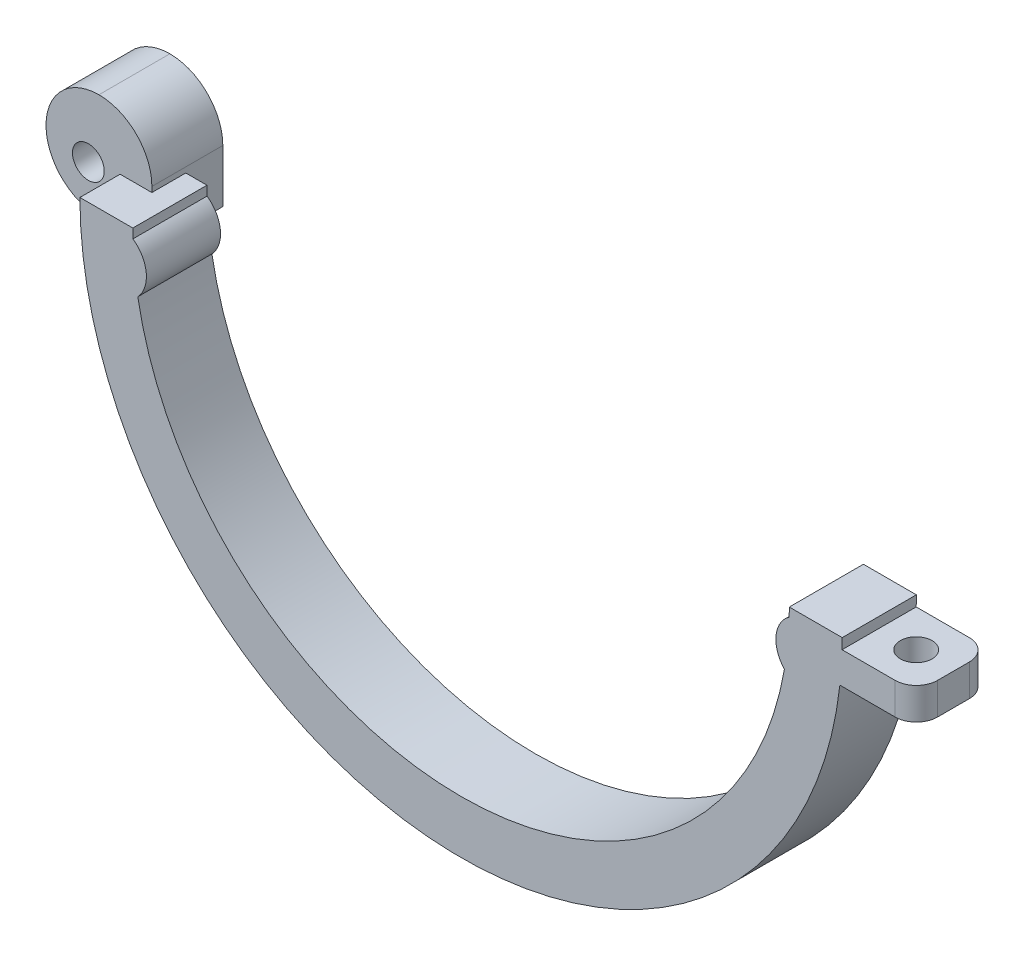
SolidWorks part; units mm, degrees
ref_plane "Front Plane" through (0, 0, 0) normal (0, 0, 1) x (1, 0, 0)
ref_plane "Top Plane" through (0, 0, 0) normal (0, 1, 0) x (1, 0, 0)
ref_plane "Right Plane" through (0, 0, 0) normal (1, 0, 0) x (0, 0, -1)
sketch "Sketch1" plane through (0, 0, 0) normal (0, 0, 1) x (1, 0, 0)
  line L0 (-36, 0) -> (36, 0)
  circle A0 centre (0, 0) radius 31
  circle A1 centre (0, 0) radius 36
  circle A2 centre (-32.7163, -3.3335) radius 3
  circle A3 centre (32.7313, -3.2727) radius 3
  dimension "D2" = 62
  dimension "D3" = 0
  dimension "D4" = 72
  dimension "D8" = 6
  dimension "D9" = 6
  dimension "D1" = 0
  dimension "D5" = 36
  dimension "D6" = 36
  dimension "D7" = 0
extrude "Boss-Extrude2" add sketch "Sketch1" along normal blind 7 contours A0 A3 | A0 A3 | A3 A0 A2 L0 A1 | A0 A2 L0 | A0 A2 | A1 region at (33.5, -0.0805, 0) region at (33.0577, -3.3053, 0) region at (30.3825, -3.0379, 0) region at (-30.373, -3.0948, 0) region at (-33.0462, -3.3672, 0)
sketch "Sketch7" plane through (0, 0, 0) normal (0, 0, -1) x (-1, 0, 0)
  line L0 (36, 0) -> (31, 0) construction
  line L1 (33, -4.5) -> (43, -4.5)
  line L2 (33, -4.5) -> (33, 5.5)
  line L3 (33, 5.5) -> (43, 5.5)
  line L4 (43, -4.5) -> (43, 5.5)
  dimension "D1" = 10
  dimension "D2" = 10
  dimension "D3" = 5.5
  dimension "D4" = 2
extrude "Boss-Extrude7" add sketch "Sketch7" against normal blind 3.2 and the other way blind 3.5
sketch "Sketch8" plane through (0, 0, 3.2) normal (0, 0, 1) x (1, 0, 0)
  line L0 (-43, -4.5) -> (-43, 5.5) construction
  line L1 (-35.7176, -4.5) -> (-43, -4.5) construction
  circle A0 centre (-39, -0.5) radius 1.5
  dimension "D1" = 3
  dimension "D2" = 4
  dimension "D3" = 4
extrude "Cut-Extrude3" cut sketch "Sketch8" against normal blind 10
fillet "Fillet1" radius 5 1 edges at (-43, 5.5, -0.15) type face fillet first side face at (-43, 0.5, -0.15) second side face at (-38, 5.5, -0.15)
fillet "Fillet2" radius 5 1 edges at (-43, -4.5, -0.15) type face fillet first side face at (-37.2392, -4.5, -0.1) second side face at (-43, -2, -0.15)
fillet "Fillet3" radius 5 1 edges at (-33, 5.5, -0.15) type face fillet first side face at (-35.5, 5.5, -0.15) second side face at (-33, 0.3333, -0.1)
sketch "Sketch9" plane through (0, 0, 7) normal (0, 0, 1) x (1, 0, 0)
  line L0 (31, 0) -> (36, 0) construction
  line L1 (43, -4) -> (35, -4)
  line L2 (43, -4) -> (43, -1)
  line L3 (43, -1) -> (35, -1)
  line L4 (35, -4) -> (35, -1)
  dimension "D1" = 4
  dimension "D2" = 3
  dimension "D3" = 8
  dimension "D4" = 1
extrude "Boss-Extrude8" add sketch "Sketch9" against normal blind 7
sketch "Sketch10" plane through (0, -1, 0) normal (0, 1, 0) x (1, 0, 0)
  line L0 (35.9861, -7) -> (35.9861, 0) construction
  line L1 (43, 0) -> (35.9861, 0) construction
  circle A0 centre (39.4861, -3.5) radius 1.5
  dimension "D1" = 3
  dimension "D2" = 3.5
  dimension "D3" = 3.5
extrude "Cut-Extrude4" cut sketch "Sketch10" against normal blind 10
fillet "Fillet4" radius 2 1 edges at (43, -2.5, 7) type face fillet first side face at (12.9936, -6.817, 7) second side face at (43, -2.5, 3.5)
fillet "Fillet5" radius 2 1 edges at (43, -2.5, 0) type face fillet first side face at (43, -2.5, 2.5) second side face at (6.5942, -6.3292, 0)
